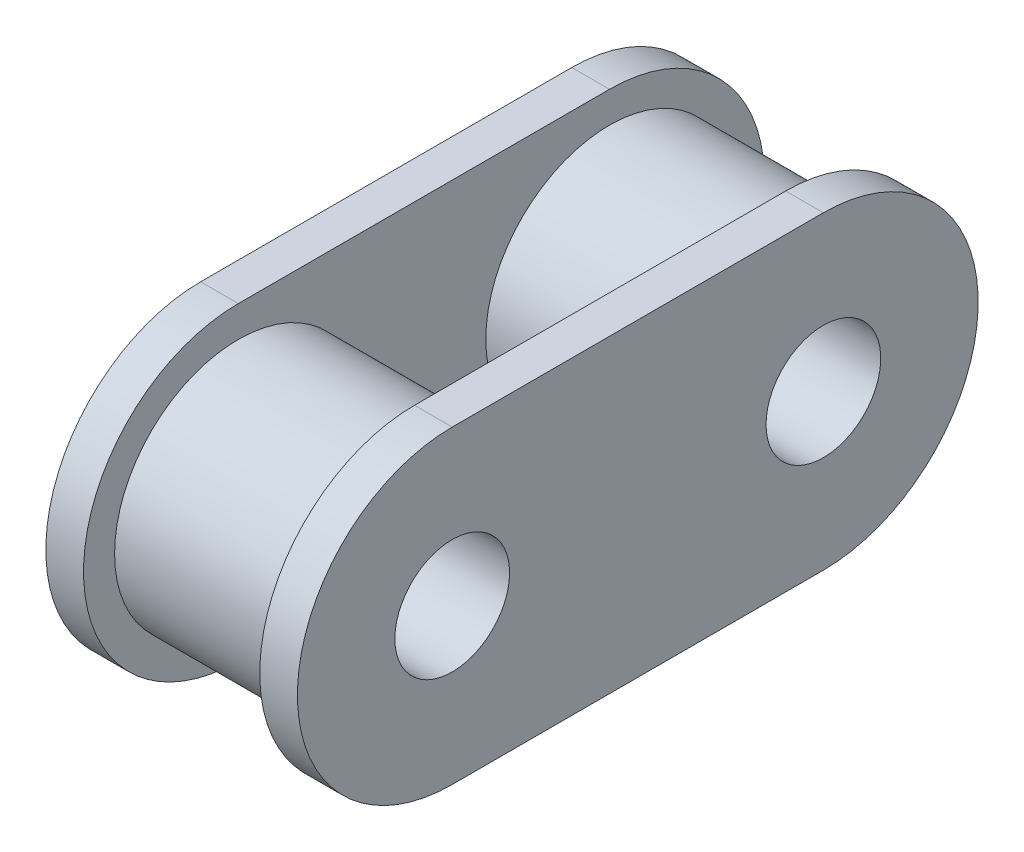
SolidWorks part; units mm, degrees
ref_plane "Front Plane" through (0, 0, 0) normal (0, 0, 1) x (1, 0, 0)
ref_plane "Top Plane" through (0, 0, 0) normal (0, 1, 0) x (1, 0, 0)
ref_plane "Right Plane" through (0, 0, 0) normal (1, 0, 0) x (0, 0, -1)
sketch "Sketch1" plane through (0, 0, 0) normal (1, 0, 0) x (0, 0, -1)
  line L0 (-3, 0) -> (3, 0) construction
  line L1 (0, 10.5372) -> (0, -10.8028) construction
  line L2 (-3, 0) -> (3, 0) construction
  line L3 (-3, 2) -> (3, 2)
  line L4 (-3, -2) -> (3, -2)
  circle A0 centre (-3, 0) radius 0.9271
  circle A1 centre (3, 0) radius 0.9271
  arc A2 (-3, 2) -> (-3, -2) centre (-3, 0) ccw
  arc A3 (3, -2) -> (3, 2) centre (3, 0) ccw
  point P7 (0, 0)
  point P8 (0, 0)
  dimension "D1" = 1.8542
  dimension "D3" = 2
  dimension "D2" = 6
extrude "Boss-Extrude1" add sketch "Sketch1" along normal mid plane 2.848
sketch "Sketch2" plane through (1.424, 0, 0) normal (1, 0, 0) x (0, 0, -1)
  line L0 (-3, -2) -> (3, -2) construction
  line L1 (3, 2) -> (-3, 2) construction
  line L2 (-3, -2) -> (3, -2)
  line L3 (3, 2) -> (-3, 2)
  line L4 (-3, 0) -> (3, 0) construction
  line L5 (-3, 2.5019) -> (3, 2.5019)
  line L6 (-3, -2.5019) -> (3, -2.5019)
  arc A0 (-3, 2) -> (-3, -2) centre (-3, 0) ccw construction
  arc A1 (3, -2) -> (3, 2) centre (3, 0) ccw construction
  arc A2 (-3, 2) -> (-3, -2) centre (-3, 0) ccw
  arc A3 (3, -2) -> (3, 2) centre (3, 0) ccw
  arc A4 (-3, 2.5019) -> (-3, -2.5019) centre (-3, 0) ccw
  arc A5 (3, -2.5019) -> (3, 2.5019) centre (3, 0) ccw
  point P3 (0, 0)
  circle M5 centre (-3, 0) radius 0.9271
  arc M6 (-3, 2) -> (-3, -2) centre (-3, 0) ccw
  line M7 (-3, -2) -> (3, -2)
  arc M8 (3, -2) -> (3, 2) centre (3, 0) ccw
  line M9 (3, 2) -> (-3, 2)
  circle M10 centre (3, 0) radius 0.9271
  dimension "D1" = 5.0038
extrude "Boss-Extrude2" add sketch "Sketch2" along normal blind 0.6096 contours M9 M6 M7 M8 M5 M10 | L6 A5 L5 A4 M6 M9 M8 M7 region at (1.424, 0, 0) region at (1.424, 2.381, 0)
mirror "Mirror1" about plane through (0, 0, 0) normal (1, 0, 0) of "Boss-Extrude2"
sketch "Sketch3" plane through (0, 0, 0) normal (1, 0, 0) x (0, 0, -1)
  line L0 (-3, 0) -> (3, 0) construction
  line L1 (-3, 2.5019) -> (3, 2.5019)
  line L2 (-3, -2.5019) -> (3, -2.5019)
  circle A0 centre (-3, 0) radius 2
  circle A1 centre (3, 0) radius 2
  arc A2 (-3, 2.5019) -> (-3, -2.5019) centre (-3, 0) ccw
  arc A3 (3, -2.5019) -> (3, 2.5019) centre (3, 0) ccw
  arc A5 (3, -2.5019) -> (3, 2.5019) centre (3, 0) ccw construction
  point P6 (0, 0)
  dimension "D1" = 4
extrude "Cut-Extrude2" cut sketch "Sketch3" against normal up to surface (1.424 mm away) and the other way up to surface (1.424 mm away) contours L2 A3 L1 A2 A0 A1 region at (0, 0, 0) up to face at (-1.424, 0, 0) other way up to face at (1.424, 0, 0)
